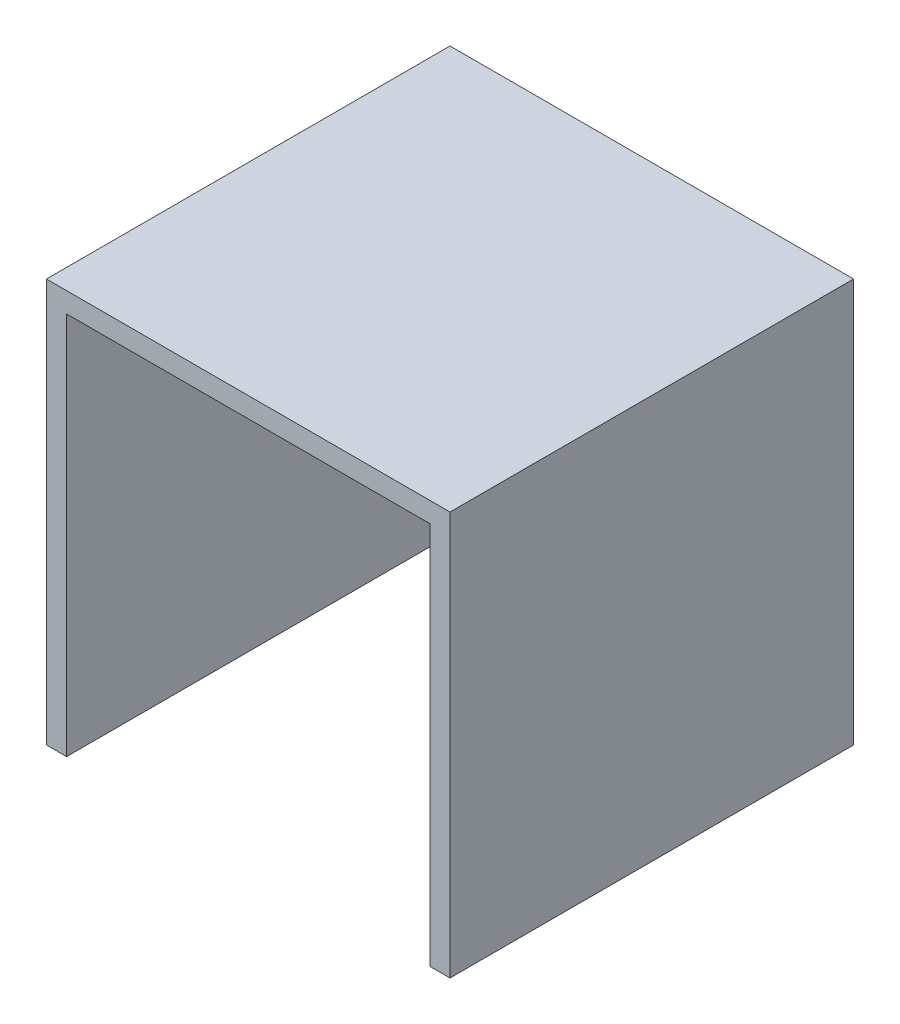
SolidWorks part; units mm, degrees
ref_plane "Front Plane" through (0, 0, 0) normal (0, 0, 1) x (1, 0, 0)
ref_plane "Top Plane" through (0, 0, 0) normal (0, 1, 0) x (1, 0, 0)
ref_plane "Right Plane" through (0, 0, 0) normal (1, 0, 0) x (0, 0, -1)
sketch "Sketch1" plane through (0, 0, 0) normal (0, 0, 1) x (1, 0, 0)
  line L0 (2, -2) -> (2, -40)
  line L1 (0, 0) -> (40, 0)
  line L2 (0, 0) -> (0, -40)
  line L3 (2, -2) -> (38, -2)
  line L4 (40, 0) -> (40, -40)
  line L5 (38, -2) -> (38, -40)
  line L6 (0, -40) -> (2, -40)
  line L7 (38, -40) -> (40, -40)
  dimension "D1" = 40
  dimension "D2" = 40
  dimension "D3" = 2
extrude "Boss-Extrude1" add sketch "Sketch1" along normal blind 40
